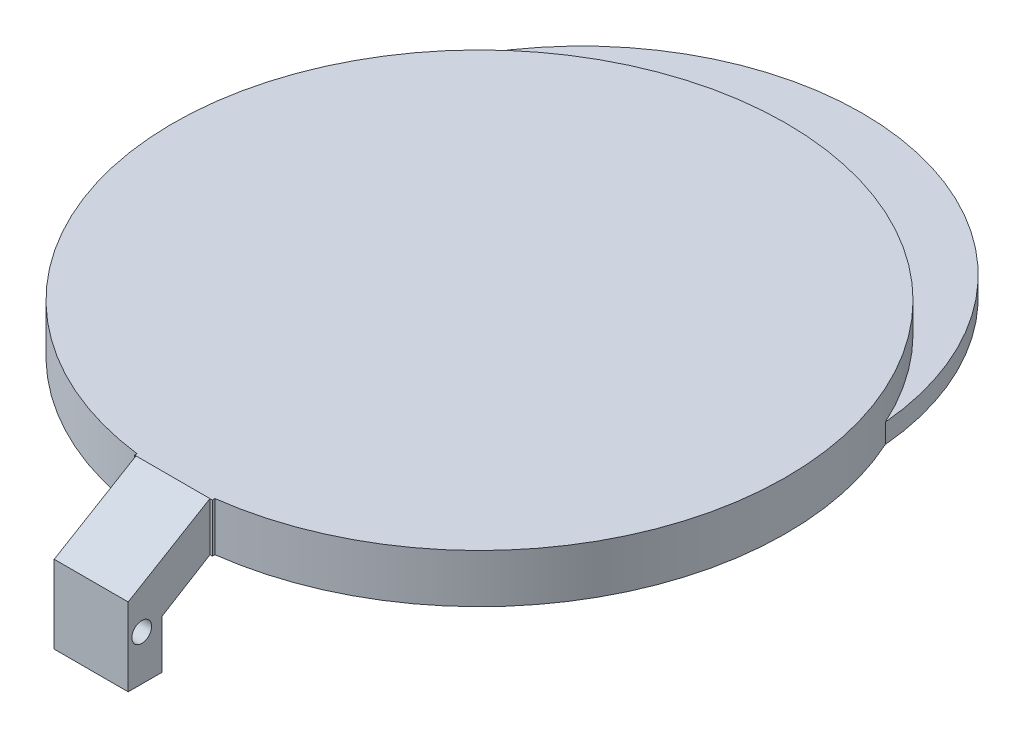
SolidWorks part; units mm, degrees
ref_plane "Front Plane" through (0, 0, 0) normal (0, 0, 1) x (1, 0, 0)
ref_plane "Top Plane" through (0, 0, 0) normal (0, 1, 0) x (1, 0, 0)
ref_plane "Right Plane" through (0, 0, 0) normal (1, 0, 0) x (0, 0, -1)
sketch "Sketch1" plane through (0, 0, 0) normal (0, 1, 0) x (1, 0, 0)
  circle A0 centre (0, 0) radius 40.005
  dimension "D1" = 80.01
extrude "Boss-Extrude1" add sketch "Sketch1" along normal blind 6.35
sketch "Sketch2" plane through (0, 0, 0) normal (0, 1, 0) x (1, 0, 0)
  circle A0 centre (0, 0) radius 40.005 construction
  arc A1 (-36.4393, 16.51) -> (36.4393, 16.51) centre (0, 13.3503) cw
  circle A3 centre (0, 0) radius 40.005
  arc A4 (-36.4393, 16.51) -> (36.4393, 16.51) centre (0, 0) ccw
  dimension "D2" = 36.576
  dimension "D1" = 0
extrude "Boss-Extrude2" add sketch "Sketch2" along normal blind 2.54
shell "Shell2" thickness 2.286 removed face at (0, 0, -4.9606)
sketch "Sketch6" plane through (0, 0, 0) normal (1, 0, 0) x (0, 0, -1)
  line L0 (-40.005, 6.35) -> (-50.673, 0)
  line L1 (-50.673, 0) -> (-50.673, -10.16)
  line L2 (-50.673, -10.16) -> (-46.228, -10.16)
  line L3 (-46.228, -10.16) -> (-46.228, -3.81)
  line L4 (-46.228, -3.81) -> (-40.005, 0)
  line L5 (-40.005, 6.35) -> (-40.005, 0)
  dimension "D1" = 10.668
  dimension "D2" = 4.445
  dimension "D3" = 6.35
  dimension "D4" = 10.16
  dimension "D5" = 6.35
extrude "Boss-Extrude3" add sketch "Sketch6" along normal mid plane 9.652 separate body
sketch "Sketch7" plane through (0, 0, 40.005) normal (0, 0, -1) x (-1, 0, 0)
  line L0 (40.005, 6.35) -> (-40.005, 6.35) construction
  line L1 (-5.1514, 0) -> (5.0086, 0)
  line L2 (-5.1514, 0) -> (-5.1514, 6.35)
  line L3 (-5.1514, 6.35) -> (5.0086, 6.35)
  line L4 (5.0086, 0) -> (5.0086, 6.35)
  line L5 (-5.1514, 0) -> (5.0086, 6.35) construction
  line L6 (-5.1514, 6.35) -> (5.0086, 0) construction
  point P0 (-0.0714, 3.175)
  dimension "D1" = 10.16
  dimension "D2" = 6.35
ref_plane "Plane1" through (0, 0, 38.1) normal (0, 0, 1) x (1, 0, 0)
sketch "Sketch9" plane through (0, 0, 38.1) normal (0, 0, 1) x (1, 0, 0)
  line L0 (-5.0086, 6.35) -> (5.1514, 6.35)
  line L1 (5.1514, 6.35) -> (5.1514, 0)
  line L2 (5.1514, 0) -> (-5.0086, 0)
  line L3 (-5.0086, 0) -> (-5.0086, 6.35)
loft "Loft1" add profiles "Sketch9", "Sketch7" connector at (-5.0086, 0, 38.1) connector at (-5.0086, 0, 40.005)
sketch "Sketch10" plane through (-4.826, 0, 0) normal (-1, 0, 0) x (0, 0, 1)
  circle A0 centre (48.9021, -4.2759) radius 1.2932
extrude "Cut-Extrude1" cut sketch "Sketch10" against normal up to next
